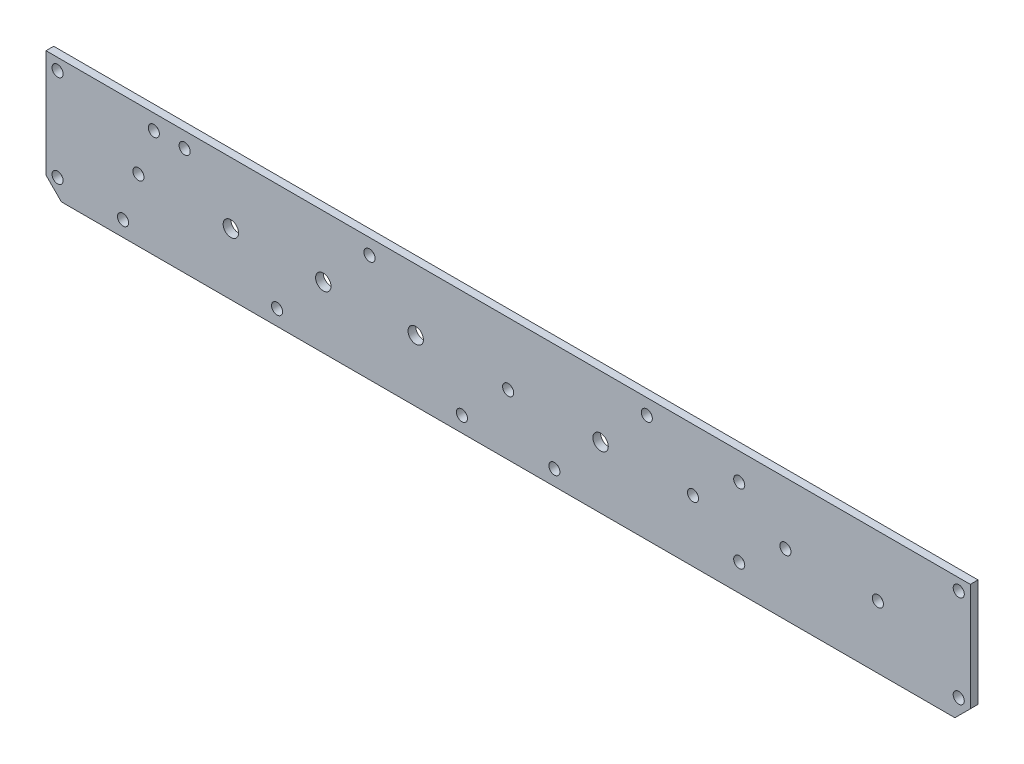
SolidWorks part; units mm, degrees
ref_plane "Front Plane" through (0, 0, 0) normal (0, 0, 1) x (1, 0, 0)
ref_plane "Top Plane" through (0, 0, 0) normal (0, 1, 0) x (1, 0, 0)
ref_plane "Right Plane" through (0, 0, 0) normal (1, 0, 0) x (0, 0, -1)
sketch "Sketch1" plane through (0, 0, 0) normal (0, 0, 1) x (1, 0, 0)
  line L1 (0, 0) -> (381, 0)
  line L2 (0, 0) -> (0, 50.8)
  line L3 (0, 50.8) -> (381, 50.8)
  line L4 (381, 0) -> (381, 50.8)
  dimension "D1" = 50.8
  dimension "D2" = 381
extrude "Boss-Extrude1" add sketch "Sketch1" along normal blind 3.175
sketch "Sketch2" plane through (0, 0, 3.175) normal (0, 0, 1) x (1, 0, 0)
  line L0 (190.5, 25.0031) -> (38.1, 25.7969) construction
  line L1 (190.5, 50.8) -> (190.5, 0) construction
  line L2 (381, 50.8) -> (0, 50.8) construction
  line L3 (0, 0) -> (381, 0) construction
  line L4 (190.5, 25.0031) -> (342.9, 25.7969) construction
  line L5 (0, 6.35) -> (0, 0)
  line L6 (0, 50.8) -> (0, 0) construction
  line L7 (0, 0) -> (6.35, 0)
  line L8 (6.35, 0) -> (0, 6.35)
  line L9 (381, 0) -> (374.65, 0)
  line L10 (374.65, 0) -> (381, 6.35)
  line L11 (381, 6.35) -> (381, 0)
  circle A0 centre (38.1, 25.7969) radius 2.286
  circle A1 centre (190.5, 25.0031) radius 2.286
  circle A2 centre (114.3, 25.4) radius 3.175
  circle A3 centre (76.2, 25.4) radius 3.175
  circle A4 centre (152.4, 25.4) radius 3.175
  circle A5 centre (228.6, 25.4) radius 3.175
  circle A6 centre (304.8, 25.4) radius 2.286
  circle A7 centre (266.7, 25.4) radius 2.286
  circle A8 centre (342.9, 25.7969) radius 2.286
  circle A9 centre (57.15, 44.45) radius 2.286
  circle A10 centre (171.45, 6.35) radius 2.286
  circle A11 centre (209.55, 6.35) radius 2.286
  circle A13 centre (133.35, 44.45) radius 2.286
  circle A14 centre (247.65, 44.45) radius 2.286
  circle A15 centre (95.25, 6.35) radius 2.286
  circle A17 centre (44.45, 44.45) radius 2.286
  circle A18 centre (31.75, 6.35) radius 2.286
  circle A19 centre (4.7625, 46.0375) radius 2.286
  circle A20 centre (4.7625, 7.9375) radius 2.286
  circle A21 centre (376.2375, 7.9375) radius 2.286
  circle A22 centre (376.2375, 46.0375) radius 2.286
  circle A24 centre (285.75, 11.1125) radius 2.286 construction
  circle A25 centre (285.75, 11.1125) radius 2.286
  circle A26 centre (285.75, 39.6875) radius 2.286
  point P17 (190.5, 25.4)
  point P63 (0, 0)
  dimension "D2" = 4.572
  dimension "D5" = 6.35
  dimension "D7" = 4.572
  dimension "D12" = 4.572
  dimension "D15" = 4.572
  dimension "D16" = 4.572
  dimension "D19" = 4.572
  dimension "D21" = 6.35
  dimension "D27" = 4.572
  dimension "D29" = 11.1125
  dimension "D1" = 0.7937
  dimension "D3" = 38.1
  dimension "D4" = 152.4
  dimension "D6" = 38.1
  dimension "D8" = 57.15
  dimension "D9" = 19.05
  dimension "D10" = 57.15
  dimension "D11" = 19.05
  dimension "D13" = 57.15
  dimension "D14" = 19.05
  dimension "D17" = 19.05
  dimension "D18" = 19.05
  dimension "D20" = 19.05
  dimension "D22" = 6.35
  dimension "D23" = 6.35
  dimension "D24" = 6.35
  dimension "D25" = 4.7625
  dimension "D26" = 4.7625
  dimension "D28" = 7.9375
extrude "Cut-Extrude1" cut sketch "Sketch2" against normal up to next (3.175 mm away)
